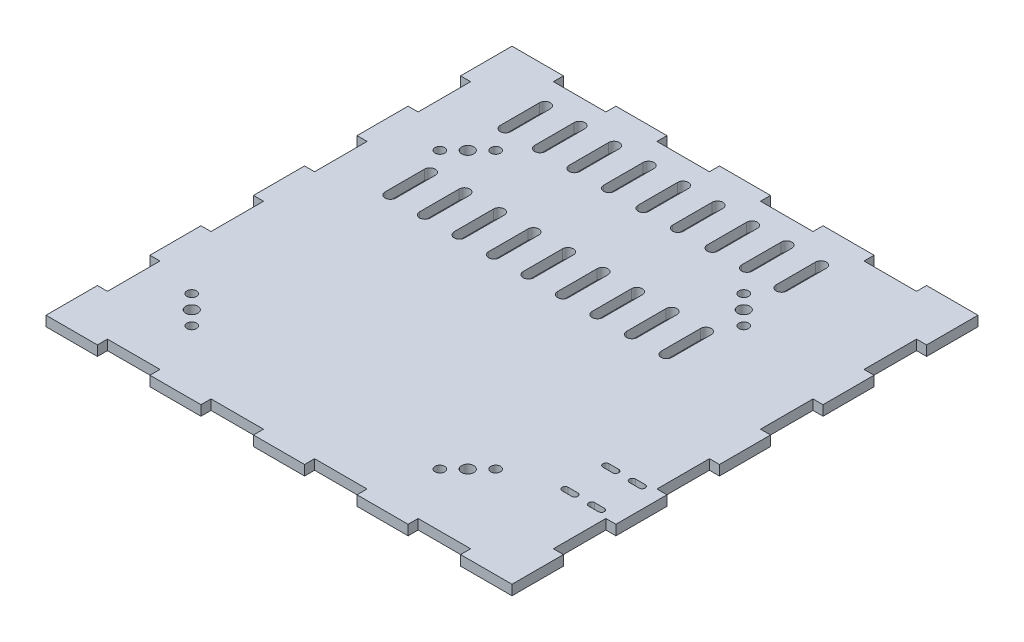
SolidWorks part; units mm, degrees
material "Acrylic (Medium-high impact)"
ref_plane "Front Plane" through (0, 0, 0) normal (0, 0, 1) x (1, 0, 0)
ref_plane "Top Plane" through (0, 0, 0) normal (0, 1, 0) x (1, 0, 0)
ref_plane "Right Plane" through (0, 0, 0) normal (1, 0, 0) x (0, 0, -1)
sketch "Board refrence" plane through (0, 0, 0) normal (0, 1, 0) x (1, 0, 0)
  line L0 (45, -19.76) -> (50, -19.76)
  line L1 (-42.5, -42.5) -> (42.5, -42.5)
  line L2 (-42.5, -42.5) -> (-42.5, 42.5)
  line L3 (-42.5, 42.5) -> (42.5, 42.5)
  line L4 (42.5, -42.5) -> (42.5, 42.5)
  line L5 (-42.5, -42.5) -> (42.5, 42.5) construction
  line L6 (-42.5, 42.5) -> (42.5, -42.5) construction
  line L7 (-50.8, 48.85) -> (50.8, 48.85)
  line L8 (-50.8, 48.85) -> (-50.8, 42.5)
  line L9 (-50.8, 42.5) -> (50.8, 42.5)
  line L10 (50.8, 48.85) -> (50.8, 42.5)
  line L11 (45, -27.76) -> (50, -27.76)
  line L12 (47.5, -27.76) -> (47.5, -19.76) construction
  circle A0 centre (-38.5, 38.5) radius 1.6
  circle A1 centre (-38.5, -38.5) radius 1.6
  circle A2 centre (38.5, -38.5) radius 1.6
  circle A3 centre (38.5, 38.5) radius 1.6
  point P0 (0, 0)
  point P14 (0, 42.5)
  point P15 (0, 42.5)
  point P26 (47.5, -23.76)
  dimension "D4" = 3.2
  dimension "D1" = 85
  dimension "D2" = 85
  dimension "D3" = 4
  dimension "D5" = 6.35
  dimension "D6" = 101.6
  dimension "D7" = 18.74
  dimension "D8" = 8
  dimension "D9" = 5
  dimension "D10" = 5
sketch "Sketch2" plane through (0, 0, 0) normal (0, 1, 0) x (1, 0, 0)
  line L0 (-42.5, -42.5) -> (-42.5, 42.5) construction
  line L1 (-54.3, 66.65) -> (69.3, 66.65) construction
  line L2 (-54.3, 66.65) -> (-54.3, -56.95) construction
  line L3 (-54.3, -56.95) -> (69.3, -56.95) construction
  line L4 (69.3, 66.65) -> (69.3, -56.95) construction
  line L6 (42.5, -42.5) -> (42.5, 42.5) construction
  line L7 (-50.8, 48.85) -> (50.8, 48.85) construction
  line L8 (-57.5, 69.85) -> (-57.5, -60.15)
  line L9 (-57.5, -60.15) -> (72.5, -60.15)
  line L10 (72.5, 69.85) -> (72.5, -60.15)
  line L11 (-57.5, 69.85) -> (72.5, 69.85)
  circle A0 centre (-38.5, 38.5) radius 1.7
  circle A1 centre (-38.5, -38.5) radius 1.7
  circle A2 centre (38.5, -38.5) radius 1.7
  circle A3 centre (38.5, 38.5) radius 1.7
  point P16 (0, 0)
  dimension "D1" = 3.4
  dimension "D2" = 15
  dimension "D3" = 21
  dimension "D4" = 30
  dimension "D6" = 130
  dimension "D5" = 3.2
extrude "Boss-Extrude1" add sketch "Sketch2" along normal blind 2.8
sketch "Sketch5" plane through (0, 2.8, 0) normal (0, 1, 0) x (1, 0, 0)
  line L0 (34.6109, 42.3891) -> (42.3891, 34.6109) construction
  line L1 (72.5, -60.15) -> (72.5, 69.85) construction
  circle A0 centre (42.3891, 34.6109) radius 1.35
  circle A1 centre (34.6109, 42.3891) radius 1.35
  circle A2 centre (34.6109, -42.3891) radius 1.35
  circle A3 centre (42.3891, -34.6109) radius 1.35
  circle A4 centre (-42.3891, -34.6109) radius 1.35
  circle A5 centre (-34.6109, -42.3891) radius 1.35
  circle A6 centre (-34.6109, 42.3891) radius 1.35
  circle A7 centre (-42.3891, 34.6109) radius 1.35
  point P4 (38.5, 38.5)
  point P23 (0, 0)
  dimension "D3" = 2.7
  dimension "D1" = 45
  dimension "D2" = 11
extrude "Cut-Extrude2" cut sketch "Sketch5" against normal up to next
sketch "Sketch4" plane through (0, 2.8, 0) normal (0, 1, 0) x (1, 0, 0)
  line L0 (72.5, 55.4056) -> (72.5, 40.9611)
  line L1 (72.5, -60.15) -> (72.5, 69.85) construction
  line L2 (72.5, 12.0722) -> (69.7, 12.0722)
  line L3 (69.7, 12.0722) -> (69.7, 26.5167)
  line L4 (69.7, 26.5167) -> (72.5, 26.5167)
  line L5 (72.5, 26.5167) -> (72.5, 12.0722)
  line L6 (72.5, -16.8167) -> (69.7, -16.8167)
  line L7 (69.7, -16.8167) -> (69.7, -2.3722)
  line L8 (69.7, -2.3722) -> (72.5, -2.3722)
  line L9 (72.5, -2.3722) -> (72.5, -16.8167)
  line L10 (72.5, 40.9611) -> (69.7, 40.9611)
  line L11 (69.7, 40.9611) -> (69.7, 55.4056)
  line L12 (69.7, 55.4056) -> (72.5, 55.4056)
  line L13 (72.5, -45.7056) -> (69.7, -45.7056)
  line L14 (69.7, -45.7056) -> (69.7, -31.2611)
  line L15 (69.7, -31.2611) -> (72.5, -31.2611)
  line L16 (72.5, -31.2611) -> (72.5, -45.7056)
  line L17 (72.5, 40.9611) -> (72.5, 12.0722) construction
  line L18 (69.7, -45.7056) -> (69.7, -60.15) construction
  line L19 (-57.5, -60.15) -> (72.5, -60.15) construction
  line L20 (69.7, -31.2611) -> (69.7, -16.8167) construction
  line L21 (72.5, 69.85) -> (-57.5, 69.85) construction
  line L42 (-57.5, 69.85) -> (72.5, -60.15) construction
  line L66 (-43.0556, -60.15) -> (-43.0556, -57.35)
  line L67 (-43.0556, -57.35) -> (-28.6111, -57.35)
  line L68 (-28.6111, -57.35) -> (-28.6111, -60.15)
  line L91 (69.7, -2.3722) -> (69.7, 12.0722) construction
  line L92 (69.7, 26.5167) -> (69.7, 40.9611) construction
  line L93 (69.7, 55.4056) -> (69.7, 69.85) construction
  line L94 (-28.6111, -60.15) -> (-43.0556, -60.15)
  line L95 (-14.1667, -60.15) -> (-14.1667, -57.35)
  line L96 (-14.1667, -57.35) -> (0.2778, -57.35)
  line L97 (0.2778, -57.35) -> (0.2778, -60.15)
  line L103 (0.2778, -60.15) -> (-14.1667, -60.15)
  line L108 (14.7222, -60.15) -> (14.7222, -57.35)
  line L113 (14.7222, -57.35) -> (29.1667, -57.35)
  line L118 (29.1667, -57.35) -> (29.1667, -60.15)
  line L119 (29.1667, -60.15) -> (14.7222, -60.15)
  line L120 (58.0556, -60.15) -> (43.6111, -60.15)
  line L121 (43.6111, -60.15) -> (43.6111, -57.35)
  line L125 (43.6111, -57.35) -> (58.0556, -57.35)
  line L126 (58.0556, -57.35) -> (58.0556, -60.15)
  line L127 (-57.5, 55.4056) -> (-54.7, 55.4056)
  line L128 (-54.7, 55.4056) -> (-54.7, 40.9611)
  line L129 (-54.7, 40.9611) -> (-57.5, 40.9611)
  line L130 (-57.5, 40.9611) -> (-57.5, 55.4056)
  line L131 (-57.5, 26.5167) -> (-54.7, 26.5167)
  line L132 (-54.7, 26.5167) -> (-54.7, 12.0722)
  line L133 (-54.7, 12.0722) -> (-57.5, 12.0722)
  line L134 (-57.5, 12.0722) -> (-57.5, 26.5167)
  line L135 (-57.5, -2.3722) -> (-54.7, -2.3722)
  line L136 (-54.7, -2.3722) -> (-54.7, -16.8167)
  line L137 (-54.7, -16.8167) -> (-57.5, -16.8167)
  line L138 (-57.5, -16.8167) -> (-57.5, -2.3722)
  line L139 (-57.5, -45.7056) -> (-57.5, -31.2611)
  line L140 (-57.5, -31.2611) -> (-54.7, -31.2611)
  line L141 (-54.7, -31.2611) -> (-54.7, -45.7056)
  line L142 (-54.7, -45.7056) -> (-57.5, -45.7056)
  line L143 (58.0556, 69.85) -> (58.0556, 67.05)
  line L144 (58.0556, 67.05) -> (43.6111, 67.05)
  line L145 (43.6111, 67.05) -> (43.6111, 69.85)
  line L146 (43.6111, 69.85) -> (58.0556, 69.85)
  line L147 (29.1667, 69.85) -> (29.1667, 67.05)
  line L148 (29.1667, 67.05) -> (14.7222, 67.05)
  line L149 (14.7222, 67.05) -> (14.7222, 69.85)
  line L150 (14.7222, 69.85) -> (29.1667, 69.85)
  line L151 (0.2778, 69.85) -> (0.2778, 67.05)
  line L152 (0.2778, 67.05) -> (-14.1667, 67.05)
  line L153 (-14.1667, 67.05) -> (-14.1667, 69.85)
  line L154 (-14.1667, 69.85) -> (0.2778, 69.85)
  line L155 (-43.0556, 69.85) -> (-28.6111, 69.85)
  line L156 (-28.6111, 69.85) -> (-28.6111, 67.05)
  line L157 (-28.6111, 67.05) -> (-43.0556, 67.05)
  line L158 (-43.0556, 67.05) -> (-43.0556, 69.85)
  point P27 (7.5, 4.85)
  point P81 (7.5, 4.85)
  dimension "D4" = 2.8
  dimension "D1" = 4
  dimension "D2" = 4
extrude "Cut-Extrude1" cut sketch "Sketch4" against normal through all
sketch "Pad reference" plane through (0, 2.8, 0) normal (0, 1, 0) x (1, 0, 0)
  line L151 (72.5, -60.15) -> (72.5, -45.7056) construction
  line L152 (72.5, 69.85) -> (58.0556, 69.85) construction
  line L153 (-50.5, -53.15) -> (-43.0556, -53.15)
  line L154 (-50.5, -45.7056) -> (-50.5, -53.15)
  line L155 (-50.5, -53.15) -> (-43.0556, -53.15) construction
  line L156 (-50.5, -45.7056) -> (-50.5, -53.15) construction
  circle A0 centre (-50.5, 62.85) radius 4
  circle A1 centre (65.5, 62.85) radius 4
  circle A2 centre (65.5, -53.15) radius 4
  circle A3 centre (-50.5, -53.15) radius 4
  dimension "D1" = 8
  dimension "D3" = 7
  dimension "D4" = 7
  dimension "D2" = 7
sketch "Sketch6" plane through (0, 2.8, 0) normal (0, 1, 0) x (1, 0, 0)
  line L0 (67, -29.7389) -> (64.3, -29.7389) construction
  line L1 (67, -30.5889) -> (64.3, -30.5889)
  line L2 (67, -28.8889) -> (64.3, -28.8889)
  line L3 (59.6, -29.7389) -> (56.9, -29.7389) construction
  line L4 (59.6, -30.5889) -> (56.9, -30.5889)
  line L5 (59.6, -28.8889) -> (56.9, -28.8889)
  line L6 (72.5, -24.0389) -> (-49927.5, -24.0389) construction
  line L7 (72.5, -31.2611) -> (72.5, -16.8167) construction
  line L8 (59.6, -18.3389) -> (56.9, -18.3389) construction
  line L9 (59.6, -17.4889) -> (56.9, -17.4889)
  line L10 (59.6, -19.1889) -> (56.9, -19.1889)
  line L11 (67, -18.3389) -> (64.3, -18.3389) construction
  line L12 (67, -17.4889) -> (64.3, -17.4889)
  line L13 (67, -19.1889) -> (64.3, -19.1889)
  arc A0 (67, -30.5889) -> (67, -28.8889) centre (67, -29.7389) ccw
  arc A1 (64.3, -28.8889) -> (64.3, -30.5889) centre (64.3, -29.7389) ccw
  arc A2 (59.6, -30.5889) -> (59.6, -28.8889) centre (59.6, -29.7389) ccw
  arc A3 (56.9, -28.8889) -> (56.9, -30.5889) centre (56.9, -29.7389) ccw
  arc A4 (59.6, -17.4889) -> (59.6, -19.1889) centre (59.6, -18.3389) cw
  arc A5 (56.9, -19.1889) -> (56.9, -17.4889) centre (56.9, -18.3389) cw
  arc A6 (67, -17.4889) -> (67, -19.1889) centre (67, -18.3389) cw
  arc A7 (64.3, -19.1889) -> (64.3, -17.4889) centre (64.3, -18.3389) cw
  point P2 (65.65, -29.7389)
  point P7 (58.25, -29.7389)
  point P18 (72.5, -24.0389)
  point P21 (58.25, -18.3389)
  point P28 (65.65, -18.3389)
  dimension "D3" = 3
  dimension "D1" = 4.4
  dimension "D2" = 1.7
  dimension "D4" = 4.85
  dimension "D5" = 5.5
extrude "Cut-Extrude3" cut sketch "Sketch6" against normal up to next
sketch "Sketch7" plane through (0, 2.8, 0) normal (0, 1, 0) x (1, 0, 0)
  line L0 (-38.5, 60.05) -> (-38.5, 49.05) construction
  line L1 (-37, 60.05) -> (-37, 49.05)
  line L2 (-40, 60.05) -> (-40, 49.05)
  line L3 (-43.0556, 67.05) -> (-28.6111, 67.05) construction
  line L5 (-30.375, 60.05) -> (-30.375, 49.05)
  line L6 (-27.375, 60.05) -> (-27.375, 49.05)
  line L7 (-28.875, 60.05) -> (-28.875, 49.05) construction
  line L8 (-20.75, 60.05) -> (-20.75, 49.05)
  line L9 (-17.75, 60.05) -> (-17.75, 49.05)
  line L10 (-19.25, 60.05) -> (-19.25, 49.05) construction
  line L11 (-11.125, 60.05) -> (-11.125, 49.05)
  line L12 (-8.125, 60.05) -> (-8.125, 49.05)
  line L13 (-9.625, 60.05) -> (-9.625, 49.05) construction
  line L14 (-1.5, 60.05) -> (-1.5, 49.05)
  line L15 (1.5, 60.05) -> (1.5, 49.05)
  line L16 (0, 60.05) -> (0, 49.05) construction
  line L17 (8.125, 60.05) -> (8.125, 49.05)
  line L18 (11.125, 60.05) -> (11.125, 49.05)
  line L19 (9.625, 60.05) -> (9.625, 49.05) construction
  line L20 (17.75, 60.05) -> (17.75, 49.05)
  line L21 (20.75, 60.05) -> (20.75, 49.05)
  line L22 (19.25, 60.05) -> (19.25, 49.05) construction
  line L23 (27.375, 60.05) -> (27.375, 49.05)
  line L24 (30.375, 60.05) -> (30.375, 49.05)
  line L25 (28.875, 60.05) -> (28.875, 49.05) construction
  line L26 (37, 60.05) -> (37, 49.05)
  line L27 (40, 60.05) -> (40, 49.05)
  line L28 (38.5, 60.05) -> (38.5, 49.05) construction
  line L31 (-40, 27.95) -> (-40, 16.95)
  line L32 (-38.5, 38.5) -> (-38.5, 49.05) construction
  line L33 (-38.5, 38.5) -> (-38.5, 27.95) construction
  line L35 (-37, 27.95) -> (-37, 16.95)
  line L36 (-38.5, 27.95) -> (-38.5, 16.95) construction
  line L37 (-30.375, 27.95) -> (-30.375, 16.95)
  line L38 (-27.375, 27.95) -> (-27.375, 16.95)
  line L39 (-28.875, 27.95) -> (-28.875, 16.95) construction
  line L40 (-20.75, 27.95) -> (-20.75, 16.95)
  line L41 (-17.75, 27.95) -> (-17.75, 16.95)
  line L42 (-19.25, 27.95) -> (-19.25, 16.95) construction
  line L43 (-11.125, 27.95) -> (-11.125, 16.95)
  line L44 (-8.125, 27.95) -> (-8.125, 16.95)
  line L45 (-9.625, 27.95) -> (-9.625, 16.95) construction
  line L46 (-1.5, 27.95) -> (-1.5, 16.95)
  line L47 (1.5, 27.95) -> (1.5, 16.95)
  line L48 (0, 27.95) -> (0, 16.95) construction
  line L49 (8.125, 27.95) -> (8.125, 16.95)
  line L50 (11.125, 27.95) -> (11.125, 16.95)
  line L51 (9.625, 27.95) -> (9.625, 16.95) construction
  line L52 (17.75, 27.95) -> (17.75, 16.95)
  line L53 (20.75, 27.95) -> (20.75, 16.95)
  line L54 (19.25, 27.95) -> (19.25, 16.95) construction
  line L55 (27.375, 27.95) -> (27.375, 16.95)
  line L56 (30.375, 27.95) -> (30.375, 16.95)
  line L57 (28.875, 27.95) -> (28.875, 16.95) construction
  line L58 (37, 27.95) -> (37, 16.95)
  line L59 (40, 27.95) -> (40, 16.95)
  line L60 (38.5, 27.95) -> (38.5, 16.95) construction
  line L61 (38.5, 27.95) -> (38.5, 38.5) construction
  line L62 (38.5, 38.5) -> (38.5, 49.05) construction
  arc A0 (-37, 60.05) -> (-40, 60.05) centre (-38.5, 60.05) ccw
  arc A1 (-40, 49.05) -> (-37, 49.05) centre (-38.5, 49.05) ccw
  arc A2 (-27.375, 60.05) -> (-30.375, 60.05) centre (-28.875, 60.05) ccw
  arc A3 (-30.375, 49.05) -> (-27.375, 49.05) centre (-28.875, 49.05) ccw
  arc A4 (-17.75, 60.05) -> (-20.75, 60.05) centre (-19.25, 60.05) ccw
  arc A5 (-20.75, 49.05) -> (-17.75, 49.05) centre (-19.25, 49.05) ccw
  arc A6 (-8.125, 60.05) -> (-11.125, 60.05) centre (-9.625, 60.05) ccw
  arc A7 (-11.125, 49.05) -> (-8.125, 49.05) centre (-9.625, 49.05) ccw
  arc A8 (1.5, 60.05) -> (-1.5, 60.05) centre (0, 60.05) ccw
  arc A9 (-1.5, 49.05) -> (1.5, 49.05) centre (0, 49.05) ccw
  arc A10 (11.125, 60.05) -> (8.125, 60.05) centre (9.625, 60.05) ccw
  arc A11 (8.125, 49.05) -> (11.125, 49.05) centre (9.625, 49.05) ccw
  arc A12 (20.75, 60.05) -> (17.75, 60.05) centre (19.25, 60.05) ccw
  arc A13 (17.75, 49.05) -> (20.75, 49.05) centre (19.25, 49.05) ccw
  arc A14 (30.375, 60.05) -> (27.375, 60.05) centre (28.875, 60.05) ccw
  arc A15 (27.375, 49.05) -> (30.375, 49.05) centre (28.875, 49.05) ccw
  arc A16 (40, 60.05) -> (37, 60.05) centre (38.5, 60.05) ccw
  arc A17 (37, 49.05) -> (40, 49.05) centre (38.5, 49.05) ccw
  arc A18 (-37, 27.95) -> (-40, 27.95) centre (-38.5, 27.95) ccw
  arc A19 (-40, 16.95) -> (-37, 16.95) centre (-38.5, 16.95) ccw
  arc A20 (-27.375, 27.95) -> (-30.375, 27.95) centre (-28.875, 27.95) ccw
  arc A21 (-30.375, 16.95) -> (-27.375, 16.95) centre (-28.875, 16.95) ccw
  arc A22 (-17.75, 27.95) -> (-20.75, 27.95) centre (-19.25, 27.95) ccw
  arc A23 (-20.75, 16.95) -> (-17.75, 16.95) centre (-19.25, 16.95) ccw
  arc A24 (-8.125, 27.95) -> (-11.125, 27.95) centre (-9.625, 27.95) ccw
  arc A25 (-11.125, 16.95) -> (-8.125, 16.95) centre (-9.625, 16.95) ccw
  arc A26 (1.5, 27.95) -> (-1.5, 27.95) centre (0, 27.95) ccw
  arc A27 (-1.5, 16.95) -> (1.5, 16.95) centre (0, 16.95) ccw
  arc A28 (11.125, 27.95) -> (8.125, 27.95) centre (9.625, 27.95) ccw
  arc A29 (8.125, 16.95) -> (11.125, 16.95) centre (9.625, 16.95) ccw
  arc A30 (20.75, 27.95) -> (17.75, 27.95) centre (19.25, 27.95) ccw
  arc A31 (17.75, 16.95) -> (20.75, 16.95) centre (19.25, 16.95) ccw
  arc A32 (30.375, 27.95) -> (27.375, 27.95) centre (28.875, 27.95) ccw
  arc A33 (27.375, 16.95) -> (30.375, 16.95) centre (28.875, 16.95) ccw
  arc A34 (40, 27.95) -> (37, 27.95) centre (38.5, 27.95) ccw
  arc A35 (37, 16.95) -> (40, 16.95) centre (38.5, 16.95) ccw
  point P2 (-38.5, 54.55)
  point P12 (-40, 54.55)
  point P16 (-28.875, 54.55)
  point P23 (-19.25, 54.55)
  point P30 (-9.625, 54.55)
  point P37 (0, 54.55)
  point P44 (9.625, 54.55)
  point P51 (19.25, 54.55)
  point P58 (28.875, 54.55)
  point P65 (38.5, 54.55)
  point P75 (-38.5, 22.45)
  point P86 (-28.875, 22.45)
  point P93 (-19.25, 22.45)
  point P100 (-9.625, 22.45)
  point P107 (0, 22.45)
  point P114 (9.625, 22.45)
  point P121 (19.25, 22.45)
  point P128 (28.875, 22.45)
  point P135 (38.5, 22.45)
  dimension "D1" = 7
  dimension "D2" = 11
  dimension "D4" = 3
  dimension "D5" = 9
  dimension "D6" = 2
extrude "Cut-Extrude4" cut sketch "Sketch7" against normal up to next
other "Tolerance" flip direction yes face at (43.6111, 1.4, -68.45) face at (14.7222, 1.4, -68.45) face at (-14.1667, 1.4, -68.45) face at (-43.0556, 1.4, -68.45) face at (29.1667, 1.4, -68.45) face at (58.0556, 1.4, -68.45) face at (0.2778, 1.4, -68.45) face at (-28.6111, 1.4, -68.45) face at (-56.1, 1.4, -40.9611) face at (-56.1, 1.4, -55.4056) face at (-56.1, 1.4, -12.0722) face at (-56.1, 1.4, -26.5167) face at (-56.1, 1.4, 2.3722) face at (-56.1, 1.4, 16.8167) face at (-56.1, 1.4, 45.7056) face at (-56.1, 1.4, 31.2611) face at (-28.6111, 1.4, 58.75) face at (-43.0556, 1.4, 58.75) face at (-14.1667, 1.4, 58.75) face at (0.2778, 1.4, 58.75) face at (14.7222, 1.4, 58.75) face at (29.1667, 1.4, 58.75) face at (58.0556, 1.4, 58.75) face at (43.6111, 1.4, 58.75) face at (71.1, 1.4, 31.2611) face at (71.1, 1.4, 45.7056) face at (71.1, 1.4, 16.8167) face at (71.1, 1.4, 2.3722) face at (71.1, 1.4, -12.0722) face at (71.1, 1.4, -26.5167) face at (71.1, 1.4, -55.4056) face at (71.1, 1.4, -40.9611) offset 0.1 parameters "D1"=0.1
equation "\"D5@Board refrence\" =  ( 1 / 4 )  * 1in"
equation "\"D6@Board refrence\" = 4in"
equation "\"slot_depth\"= 2.8mm"
equation "\"slot_width_tolerance\"= 0.0mm"
equation "\"D4@Sketch4\"=\"slot_depth\""
